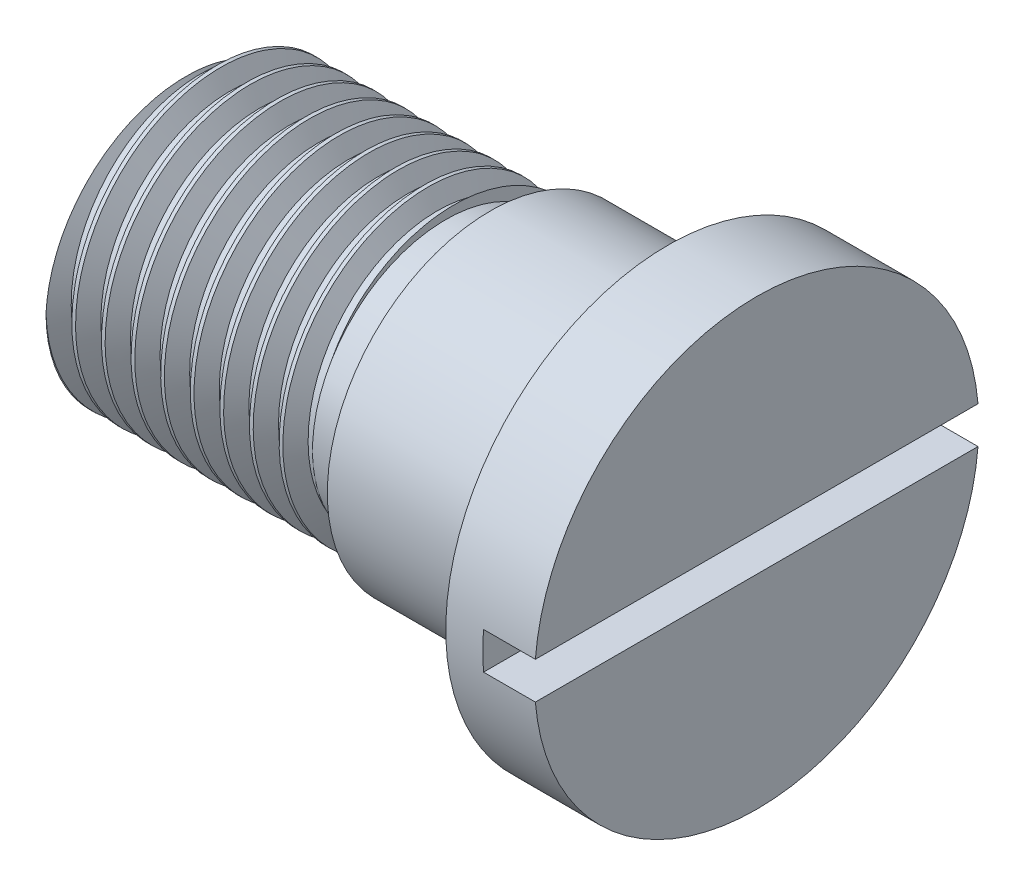
SolidWorks part; units mm, degrees
ref_plane "Front Plane" through (0, 0, 0) normal (0, 0, 1) x (1, 0, 0)
ref_plane "Top Plane" through (0, 0, 0) normal (0, 1, 0) x (1, 0, 0)
ref_plane "Right Plane" through (0, 0, 0) normal (1, 0, 0) x (0, 0, -1)
sketch "Sketch1" plane through (0, 0, 0) normal (0, 0, 1) x (1, 0, 0)
  line L0 (0, 0) -> (-38, 0) construction
  line L1 (0, 15) -> (-6, 15)
  line L2 (-6, 15) -> (-6, 11)
  line L3 (-6, 11) -> (-18, 11)
  line L4 (-18, 11) -> (-18, 9)
  line L5 (-18, 9) -> (-21, 9)
  line L6 (-21, 9) -> (-21, 10)
  line L7 (-21, 10) -> (-38, 10)
  line L8 (-38, 10) -> (-38, 0)
  line L9 (0, 15) -> (0, 0)
  line L10 (0, 0) -> (-38, 0)
  dimension "D1" = 38
  dimension "D2" = 30
  dimension "D3" = 6
  dimension "D4" = 22
  dimension "D5" = 12
  dimension "D6" = 18
  dimension "D7" = 3
  dimension "D8" = 20
revolve "Revolve1" add sketch "Sketch1" angle 360 about L0
thread "Thread1" pitch 2 method cut trim with start face yes trim with end face yes profile "Thread Profile1" start angle 0, offset 5, length 0, pitch 2, diameter 20
ref_plane "Plane1" through (-43, 0, -10) normal (0, -1, 0) x (0, 0, -1)
sketch "Thread Profile1" plane through (-43, 0, -10) normal (0, -1, 0) x (0, 0, -1)
  line L0 (0, 0) -> (0, 2) construction
  line L11 (0, 0) -> (0, 1.75)
  line L12 (0, 1.75) -> (-1.0825, 1.125)
  line L13 (-1.0825, 1.125) -> (-1.0825, 0.625)
  line L15 (-1.0825, 0.625) -> (0, 0)
  line L17 (-1.0825, 0.875) -> (0, 0.875) construction
  point P2 (0, 0)
  dimension "Pitch" = 2
  dimension "Profile_Angle" = 60
  dimension "Profile_Land" = 0.5
  dimension "Profile_Height" = 1.0825
sketch "Sketch5" plane through (0, 0, 0) normal (1, 0, 0) x (0, 0, -1)
  line L1 (-21.2886, -1.25) -> (21.2886, -1.25)
  line L2 (-21.2886, -1.25) -> (-21.2886, 1.25)
  line L3 (-21.2886, 1.25) -> (21.2886, 1.25)
  line L4 (21.2886, -1.25) -> (21.2886, 1.25)
  line L5 (-21.2886, -1.25) -> (21.2886, 1.25) construction
  line L6 (-21.2886, 1.25) -> (21.2886, -1.25) construction
  point P0 (0, 0)
  dimension "D1" = 2.5
extrude "Cut-Extrude1" cut sketch "Sketch5" against normal blind 3.5
